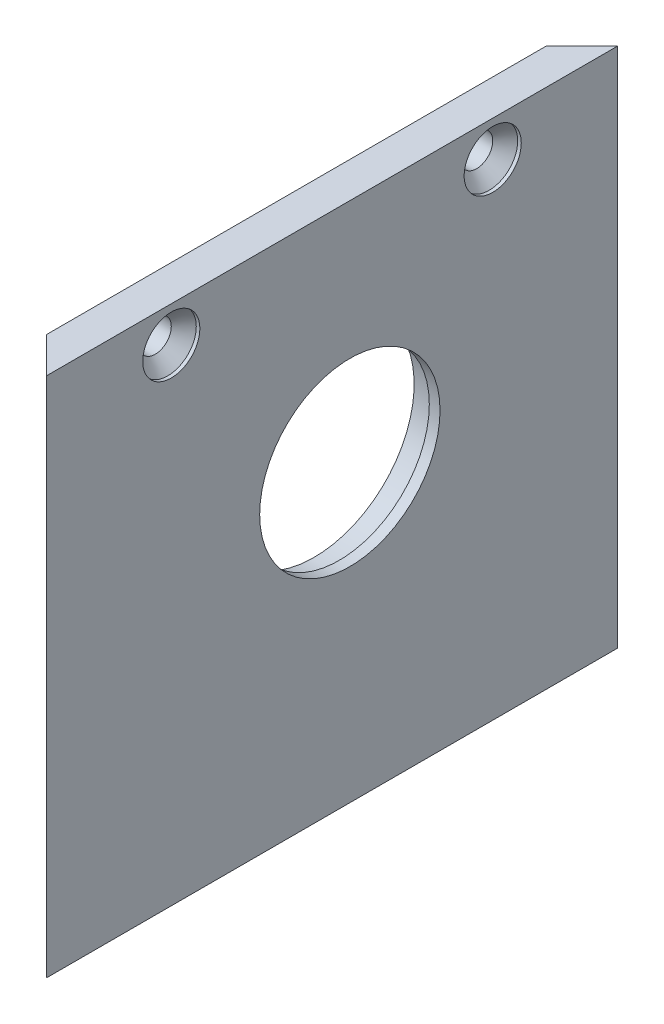
SolidWorks part; units mm, degrees
material "Oak"
ref_plane "Front Plane" through (0, 0, 0) normal (0, 0, 1) x (1, 0, 0)
ref_plane "Top Plane" through (0, 0, 0) normal (0, 1, 0) x (1, 0, 0)
ref_plane "Right Plane" through (0, 0, 0) normal (1, 0, 0) x (0, 0, -1)
sketch "Sketch1" plane through (0, 0, 0) normal (1, 0, 0) x (0, 0, -1)
  line L1 (-80, 73) -> (80, 73)
  line L2 (-80, 73) -> (-80, -73)
  line L3 (-80, -73) -> (80, -73)
  line L4 (80, 73) -> (80, -73)
  line L5 (-80, 73) -> (80, -73) construction
  line L6 (-80, -73) -> (80, 73) construction
  point P0 (0, 0)
  dimension "D1" = 146
  dimension "D2" = 160
extrude "Boss-Extrude1" add sketch "Sketch1" along normal blind 10
sketch "Sketch2" plane through (0, 0, 0) normal (-1, 0, 0) x (0, 0, 1)
  circle A0 centre (-5, 9.5) radius 25.25
  dimension "D1" = 50.5
extrude "Cut-Extrude1" cut sketch "Sketch2" against normal blind 10
chamfer "Chamfer1" distance 10 angle 45 2 edges at (0, 0, -80) (0, 0, 80)
sketch "Sketch3" plane through (0, 0, 0) normal (-1, 0, 0) x (0, 0, 1)
  circle A0 centre (-5, 9.5) radius 28
  dimension "D1" = 56
extrude "Cut-Extrude2" cut sketch "Sketch3" against normal blind 7
sketch "Sketch8" plane through (10, 0, 0) normal (1, 0, 0) x (0, 0, -1)
  circle A0 centre (45, 63) radius 2.75
  circle A1 centre (-45, 63) radius 2.75
  dimension "D1" = 5.5
extrude "Cut-Extrude3" cut sketch "Sketch8" against normal through all
hole_wizard "CSK for M8 Hex Socket Countersunk Head Screw1" positions "Sketch9" profile "Sketch11" countersink size "M8" standard "DIN" end condition through all
sketch "Sketch9" plane through (10, 0, 0) normal (1, 0, 0) x (0, 0, -1)
  point P0 (-45, 63)
  point P3 (45, 63)
sketch "Sketch11" plane through (10, 63, 45) normal (0, 1, 0) x (0, 0, -1)
  line L0 (0, 0) -> (0, 10)
  line L1 (0, 10) -> (4.5, 10)
  line L2 (4.5, 10) -> (4.5, 4.5)
  line L3 (4.5, 4.5) -> (8, 1)
  line L4 (8, 1) -> (8, 0)
  line L6 (8, 0) -> (0, 0)
  line L7 (-4.5, 4.5) -> (-8, 1) construction
  line L11 (0, -6.35) -> (0, 107.95) construction
  dimension "Thru Hole Dia." = 9
  dimension "Thru Hole Depth" = 10
  dimension "C'Sink Dia." = 16
  dimension "C'Sink Angle" = 90
  dimension "Head Clearance" = 1
sketch "Sketch12" plane through (10, 0, 0) normal (1, 0, 0) x (0, 0, -1)
  circle A0 centre (-60, 27) radius 2.75
  circle A1 centre (-60, -46) radius 2.75
  circle A2 centre (-20, -46) radius 2.75
  dimension "D1" = 5.5
extrude "Cut-Extrude4" [suppressed] cut sketch "Sketch12" against normal blind 10
